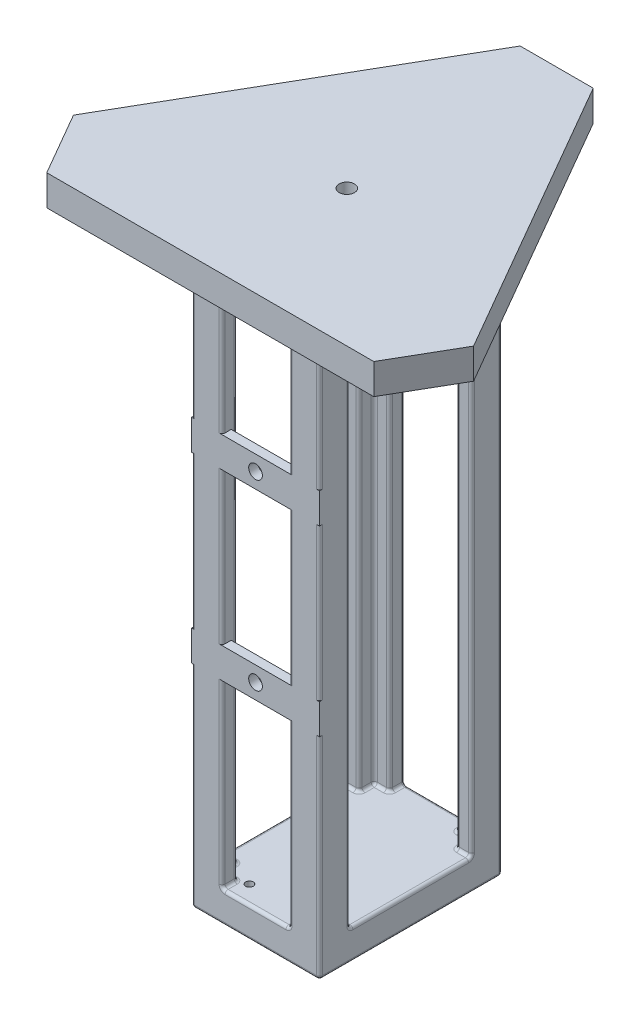
SolidWorks part; units mm, degrees
ref_plane "Plan de face" through (0, 0, 0) normal (0, 0, 1) x (1, 0, 0)
ref_plane "Plan de dessus" through (0, 0, 0) normal (0, 1, 0) x (1, 0, 0)
ref_plane "Plan de droite" through (0, 0, 0) normal (1, 0, 0) x (0, 0, -1)
sketch "Esquisse1" plane through (0, 0, 0) normal (0, 1, 0) x (1, 0, 0)
  line L29 (-12, 68.9638) -> (12, 68.9638)
  line L30 (65.7244, -24.0896) -> (53.7244, -44.8742)
  line L31 (-53.7244, -44.8742) -> (-65.7244, -24.0896)
  line L32 (-12, 68.9638) -> (-65.7244, -24.0896)
  line L33 (-53.7244, -44.8742) -> (53.7244, -44.8742)
  line L34 (65.7244, -24.0896) -> (12, 68.9638)
  circle A7 centre (0, 0) radius 2.5
  point P5 (0, 0)
  point P7 (-41.1701, 21.8833)
  point P9 (143.666, 23.8704)
  point P17 (0, 0)
  dimension "D1" = 24
  dimension "D4" = 24
  dimension "D5" = 70
  dimension "D6" = 70
  dimension "D3" = 70
  dimension "D9" = 5
  dimension "D2" = 24
  dimension "D7" = 60
  dimension "D8" = 60
  dimension "D10" = 70
  dimension "D11" = 70
extrude "Boss.-Extru.1" add sketch "Esquisse1" along normal mid plane 10
sketch "Esquisse3" plane through (0, -5, 0) normal (0, -1, 0) x (1, 0, 0)
  line L68 (21, 30) -> (11, 30)
  line L69 (21, -30) -> (-21, -30) construction
  line L70 (21, -30) -> (21, 30) construction
  line L71 (21, 30) -> (-21, 30) construction
  line L72 (-21, -30) -> (-21, 30) construction
  line L73 (21, -20) -> (16, -20)
  line L74 (16, -20) -> (16, -25)
  line L75 (11, 30) -> (11, 25)
  line L76 (11, 25) -> (16, 25)
  line L77 (16, 25) -> (16, 20)
  line L78 (16, 20) -> (21, 20)
  line L79 (21, 20) -> (21, 30)
  line L80 (21, -30) -> (21, -20)
  line L81 (16, -25) -> (11, -25)
  line L82 (11, -25) -> (11, -30)
  line L83 (-21, -30) -> (-21, -20)
  line L84 (-21, -20) -> (-16, -20)
  line L85 (-16, -20) -> (-16, -25)
  line L86 (-16, -25) -> (-11, -25)
  line L87 (-11, -25) -> (-11, -30)
  line L88 (-11, -30) -> (-21, -30)
  line L89 (-21, 30) -> (-21, 20)
  line L90 (-21, 20) -> (-16, 20)
  line L91 (-16, 20) -> (-16, 25)
  line L92 (-16, 25) -> (-11, 25)
  line L93 (-11, 25) -> (-11, 30)
  line L94 (-11, 30) -> (-21, 30)
  line L95 (11, -30) -> (21, -30)
  point P0 (0, 0)
  dimension "D1" = 42
  dimension "D2" = 60
  dimension "D3" = 10
  dimension "D4" = 10
  dimension "D5" = 5
  dimension "D6" = 5
  dimension "D7" = 25
  dimension "D8" = 5
  dimension "D9" = 5
  dimension "D10" = 5
  dimension "D11" = 10
  dimension "D12" = 5
  dimension "D13" = 5
  dimension "D14" = 5
  dimension "D15" = 10
  dimension "D16" = 16
extrude "Boss.-Extru.2" add sketch "Esquisse3" along normal blind 180
sketch "Esquisse7" plane through (0, -185, 0) normal (0, -1, 0) x (1, 0, 0)
  line L12 (21, -30) -> (-21, 30) construction
  line L13 (21, 30) -> (-21, -30) construction
  line L15 (21, -30) -> (-21, -30)
  line L16 (21, -30) -> (21, 30)
  line L17 (21, 30) -> (-21, 30)
  line L18 (-21, -30) -> (-21, 30)
  line L19 (21, -30) -> (-21, 30) construction
  line L20 (21, 30) -> (-21, -30) construction
  point P0 (0, 0)
  point P9 (0, 0)
  dimension "D1" = 42
  dimension "D2" = 60
extrude "Boss.-Extru.3" add sketch "Esquisse7" along normal blind 10
fillet "Congé3" radius 1 72 edges at (-18.5, -185, 20) (-18.5, -5, 20) (-16, -95, 20) (-16, -185, 22.5) (-16, -5, 22.5) (-16, -95, 25) (-13.5, -185, 25) (-13.5, -5, 25) (-11, -95, 25) (-11, -185, 27.5) (-11, -5, 27.5) (18.5, -185, -20) (18.5, -5, -20) (16, -95, -20) (16, -185, -22.5) (16, -5, -22.5) (16, -95, -25) (13.5, -185, -25) (13.5, -5, -25) (11, -95, -25) (11, -185, -27.5) (11, -5, -27.5) (11, -185, 27.5) (11, -5, 27.5) (11, -95, 25) (13.5, -185, 25) (13.5, -5, 25) (16, -95, 25) (16, -185, 22.5) (16, -5, 22.5) (16, -95, 20) (18.5, -185, 20) (18.5, -5, 20) (-11, -185, -27.5) (-11, -5, -27.5) (-11, -95, -25) (-13.5, -185, -25) (-13.5, -5, -25) (-16, -95, -25) (-16, -185, -22.5) (-16, -5, -22.5) (-16, -95, -20) (-18.5, -185, -20) (-18.5, -5, -20) (21, -5, 25) (21, -95, 20) (21, -95, -20) (21, -5, -25) (11, -95, -30) (-11, -95, -30) (-16, -5, -30) (21, -100, -30) (16, -5, -30) (-21, -100, -30) (-21, -5, -25) (-21, -95, -20) (-21, -95, 20) (-21, -5, 25) (-11, -95, 30) (11, -95, 30) (16, -5, 30) (21, -100, 30) (-21, -100, 30) (-16, -5, 30) (21, -195, 0) (21, -185, 0) (0, -185, -30) (0, -195, -30) (-21, -195, 0) (-21, -185, 0) (0, -185, 30) (0, -195, 30)
sketch "Esquisse8" plane through (0, -195, 0) normal (0, -1, 0) x (1, 0, 0)
  line L1 (0, -55) -> (0, 55) construction
  line L3 (20, 29) -> (-20, 29) construction
  circle A0 centre (8, 24) radius 1.25
  circle A1 centre (-8, 24) radius 1.25
  dimension "D2" = 2.5
  dimension "D1" = 8
  dimension "D3" = 5
extrude "Enlèv. mat.-Extru.4" cut sketch "Esquisse8" against normal up to next
sketch "Esquisse12" plane through (0, 0, 30) normal (0, 0, 1) x (1, 0, 0)
  line L0 (-21, -55.62) -> (21, -55.62)
  line L1 (-21, -55.62) -> (-21, -65.62)
  line L2 (-21, -65.62) -> (21, -65.62)
  line L3 (21, -55.62) -> (21, -65.62)
  line L4 (-21, -115.62) -> (21, -115.62)
  line L5 (-21, -115.62) -> (-21, -125.62)
  line L6 (-21, -125.62) -> (21, -125.62)
  line L7 (21, -115.62) -> (21, -125.62)
  line L8 (21, -6) -> (21, -194) construction
  line L9 (-21, -194) -> (-21, -6) construction
  line L10 (10, -186) -> (-10, -186) construction
  circle A0 centre (0, -60.62) radius 2.25
  circle A1 centre (0, -120.62) radius 2.25
  point P4 (21, -60.62)
  point P9 (21, -120.62)
  point P20 (0, 0)
  dimension "D6" = 4.5
  dimension "D7" = 4.5
  dimension "D1" = 10
  dimension "D2" = 10
  dimension "D3" = 60
  dimension "D4" = 125.38
  dimension "D5" = 5
  dimension "D8" = 5
extrude "Boss.-Extru.5" add sketch "Esquisse12" against normal blind 3
